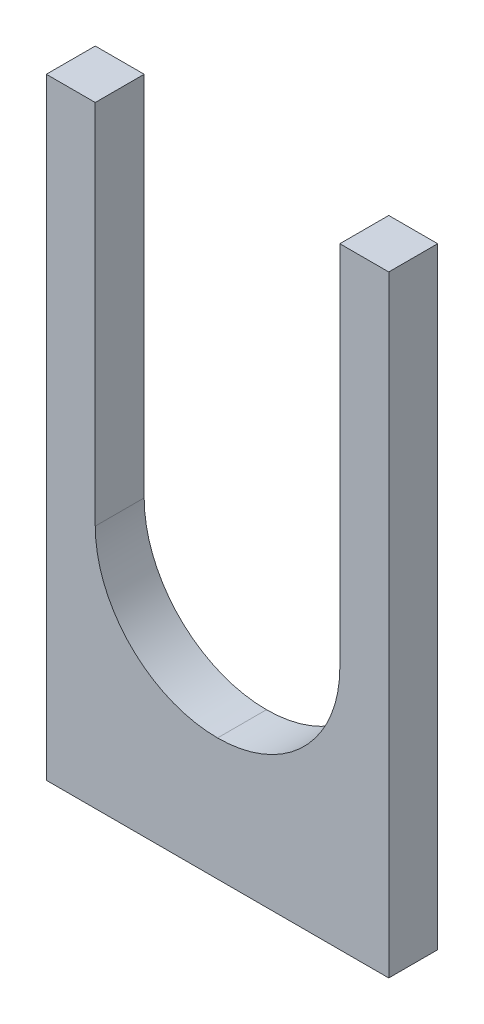
SolidWorks part; units mm, degrees
ref_plane "Front Plane" through (0, 0, 0) normal (0, 0, 1) x (1, 0, 0)
ref_plane "Top Plane" through (0, 0, 0) normal (0, 1, 0) x (1, 0, 0)
ref_plane "Right Plane" through (0, 0, 0) normal (1, 0, 0) x (0, 0, -1)
sketch "Sketch1" plane through (0, 0, 0) normal (0, 0, 1) x (1, 0, 0)
  line L0 (-25, 50) -> (-35, 50)
  line L1 (-25, -50) -> (25, -50)
  line L2 (-25, -50) -> (-25, 50)
  line L3 (-25, 50) -> (25, 50)
  line L4 (25, -50) -> (25, 50)
  line L5 (-25, -50) -> (25, 50) construction
  line L6 (-25, 50) -> (25, -50) construction
  line L7 (-35, 50) -> (-35, -75)
  line L8 (-35, -75) -> (35, -75)
  line L9 (35, -75) -> (35, 50)
  line L10 (35, 50) -> (25, 50)
  point P0 (0, 0)
  dimension "D1" = 50
  dimension "D2" = 100
  dimension "D3" = 125
  dimension "D4" = 70
extrude "Boss-Extrude1" add sketch "Sketch1" along normal blind 10 contours L9 L10 L4 L1 L2 L0 L7 L8 region at (-26.4327, 0, 0)
fillet "Fillet1" radius 25 2 edges at (25, -50, 5) (-25, -50, 5)
